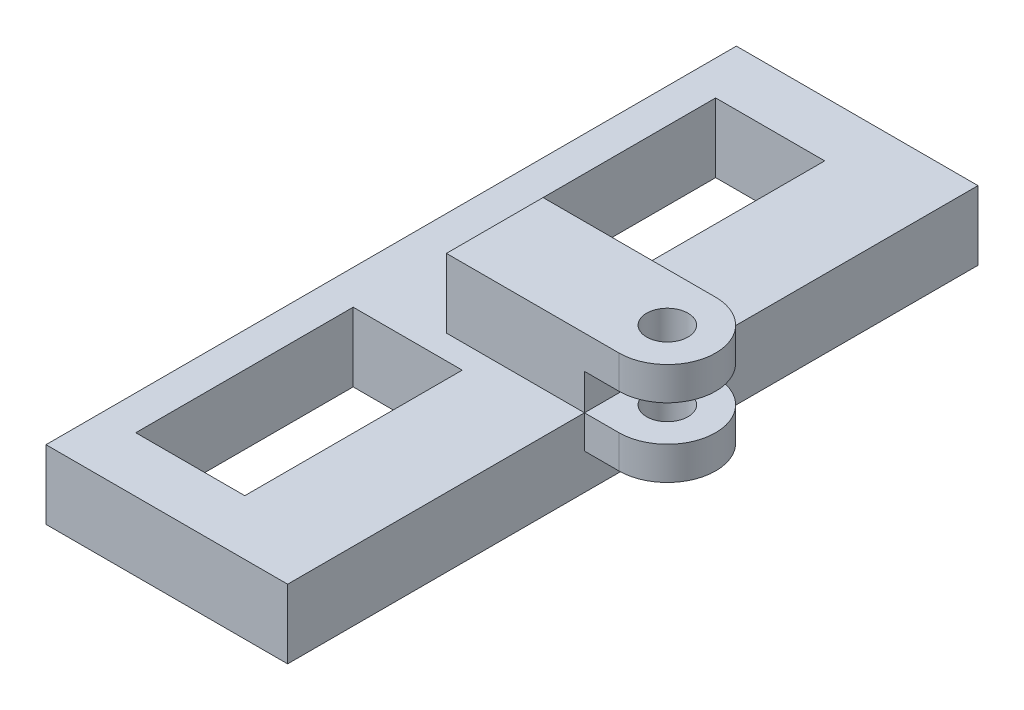
SolidWorks part; units mm, degrees
ref_plane "Front Plane" through (0, 0, 0) normal (0, 0, 1) x (1, 0, 0)
ref_plane "Top Plane" through (0, 0, 0) normal (0, 1, 0) x (1, 0, 0)
ref_plane "Right Plane" through (0, 0, 0) normal (1, 0, 0) x (0, 0, -1)
sketch "Sketch1" plane through (0, 0, 0) normal (0, 1, 0) x (1, 0, 0)
  line L1 (-22.225, 63.5) -> (22.225, 63.5)
  line L2 (-22.225, 63.5) -> (-22.225, -63.5)
  line L3 (-22.225, -63.5) -> (22.225, -63.5)
  line L4 (22.225, 63.5) -> (22.225, -63.5)
  line L5 (-22.225, 63.5) -> (22.225, -63.5) construction
  line L6 (-22.225, -63.5) -> (22.225, 63.5) construction
  line L7 (-15.875, 53.34) -> (4.185, 53.34)
  line L8 (-15.875, 53.34) -> (-15.875, 13.34)
  line L9 (-15.875, 13.34) -> (4.185, 13.34)
  line L10 (4.185, 53.34) -> (4.185, 13.34)
  line L11 (-15.875, -13.34) -> (4.185, -13.34)
  line L12 (-15.875, -13.34) -> (-15.875, -53.34)
  line L13 (-15.875, -53.34) -> (4.185, -53.34)
  line L14 (4.185, -13.34) -> (4.185, -53.34)
  point P1 (0, 0)
  dimension "D1" = 127
  dimension "D2" = 44.45
  dimension "D3" = 20.06
  dimension "D4" = 20.06
  dimension "D5" = 40
  dimension "D6" = 40
  dimension "D7" = 6.35
  dimension "D8" = 10.16
  dimension "D9" = 6.35
  dimension "D10" = 10.16
extrude "Boss-Extrude1" add sketch "Sketch1" along normal blind 12.7
sketch "Sketch2" plane through (0, 12.7, 0) normal (0, 1, 0) x (1, 0, 0)
  line L0 (28.575, 8.89) -> (-3.175, 8.89)
  line L1 (-3.175, 8.89) -> (-3.175, -8.89)
  line L2 (-3.175, -8.89) -> (28.575, -8.89)
  line L3 (22.225, -63.5) -> (22.225, 63.5) construction
  line L5 (-22.225, -63.5) -> (22.225, -63.5) construction
  arc A0 (28.575, -8.89) -> (28.575, 8.89) centre (28.575, 0) ccw
  circle A1 centre (28.575, 0) radius 3.81
  dimension "D1" = 17.78
  dimension "D2" = 7.62
  dimension "D3" = 6.35
  dimension "D4" = 63.5
  dimension "D5" = 25.4
extrude "Boss-Extrude2" add sketch "Sketch2" along normal blind 12.7 and the other way blind 12.7
sketch "Sketch3" plane through (0, 0, 8.89) normal (0, 0, 1) x (1, 0, 0)
  line L0 (37.465, 0) -> (37.465, 25.4) construction
  line L1 (22.225, 19.304) -> (37.465, 19.304)
  line L2 (22.225, 19.304) -> (22.225, 12.7)
  line L3 (22.225, 12.7) -> (37.465, 12.7)
  line L4 (37.465, 19.304) -> (37.465, 12.7)
  line L5 (22.225, 12.7) -> (22.225, 0) construction
  line L6 (37.465, 0) -> (22.225, 0)
  line L7 (37.465, 0) -> (37.465, 6.604)
  line L8 (37.465, 6.604) -> (22.225, 6.604)
  line L9 (22.225, 0) -> (22.225, 6.604)
  line L10 (37.465, 25.4) -> (28.575, 25.4) construction
  dimension "D1" = 6.604
  dimension "D2" = 6.604
  dimension "D3" = 0
  dimension "D4" = 0
  dimension "D5" = 6.096
extrude "Cut-Extrude1" cut sketch "Sketch3" against normal blind 23.114
